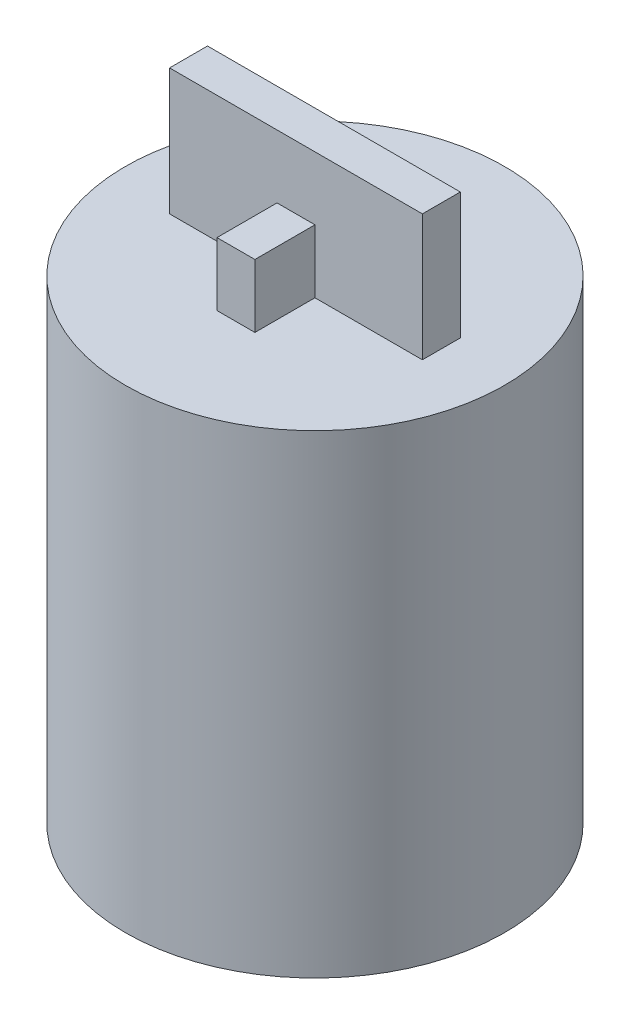
SolidWorks part; units mm, degrees
ref_plane "前视基准面" through (0, 0, 0) normal (0, 0, 1) x (1, 0, 0)
ref_plane "上视基准面" through (0, 0, 0) normal (0, 1, 0) x (1, 0, 0)
ref_plane "右视基准面" through (0, 0, 0) normal (1, 0, 0) x (0, 0, -1)
other "Configuration Table"
sketch "草图1" plane through (0, 0, 0) normal (0, 1, 0) x (1, 0, 0)
  line L1 (-2, 0.3) -> (2, 0.3)
  line L2 (-2, 0.3) -> (-2, -0.3)
  line L3 (-2, -0.3) -> (2, -0.3)
  line L4 (2, 0.3) -> (2, -0.3)
  line L5 (-2, 0.3) -> (2, -0.3) construction
  line L6 (-2, -0.3) -> (2, 0.3) construction
  line L7 (-0.3, -1.25) -> (0.3, -1.25)
  line L8 (-0.3, -1.25) -> (-0.3, 1.25)
  line L9 (-0.3, 1.25) -> (0.3, 1.25)
  line L10 (0.3, -1.25) -> (0.3, 1.25)
  line L11 (-0.3, -1.25) -> (0.3, 1.25) construction
  line L12 (-0.3, 1.25) -> (0.3, -1.25) construction
  circle A0 centre (0, 0) radius 3
  point P0 (0, 0)
  point P5 (0, 0)
  point P10 (0, 0)
  point P14 (0, 0)
  dimension "D4" = 6
  dimension "D1" = 4
  dimension "D2" = 2.5
  dimension "D3" = 0.6
extrude "凸台-拉伸1" add sketch "草图1" along normal blind 2 contours L1 L4 L3 L2
extrude "凸台-拉伸2" add sketch "草图1<3>" along normal blind 1 contours L9 L10 L7 L8
sketch "草图1<3>" plane through (0, 0, 0) normal (0, 1, 0) x (1, 0, 0) same geometry as "草图1"
extrude "凸台-拉伸3" add sketch "草图1<4>" against normal blind 7.5 contours A0
sketch "草图1<4>" plane through (0, 0, 0) normal (0, 1, 0) x (1, 0, 0) same geometry as "草图1"
sketch "草图2" plane through (0, -7.5, 0) normal (0, -1, 0) x (1, 0, 0)
  line L1 (1.13, -2.23) -> (-1.13, -2.23)
  line L2 (1.13, -2.23) -> (1.13, 2.23)
  line L3 (1.13, 2.23) -> (-1.13, 2.23)
  line L4 (-1.13, -2.23) -> (-1.13, 2.23)
  line L5 (1.13, -2.23) -> (-1.13, 2.23) construction
  line L6 (1.13, 2.23) -> (-1.13, -2.23) construction
  line L7 (2.23, 1.13) -> (-2.23, 1.13)
  line L8 (2.23, 1.13) -> (2.23, -1.13)
  line L9 (2.23, -1.13) -> (-2.23, -1.13)
  line L10 (-2.23, 1.13) -> (-2.23, -1.13)
  line L11 (2.23, 1.13) -> (-2.23, -1.13) construction
  line L12 (2.23, -1.13) -> (-2.23, 1.13) construction
  circle A0 centre (0, 0) radius 2.5
  point P2 (0, 0)
  point P4 (0, 0)
  point P13 (0, 0)
  point P14 (0, 0)
  point P15 (0, 0)
  dimension "D1" = 5
  dimension "D2" = 1.1
extrude "切除-拉伸1" cut sketch "草图2" against normal offset from surface (6.5 mm away) 1 contours L8 A0 | L3 A0 | L10 A0 | L1 A0 | L2 L3 L4 L1 | L9 L10 L7 L8 region at (0, -7.5, -2.3385) region at (2.3385, -7.5, 0) region at (-2.3385, -7.5, 0) region at (0, -7.5, 2.3385) up to face at (0, 0, 0)
